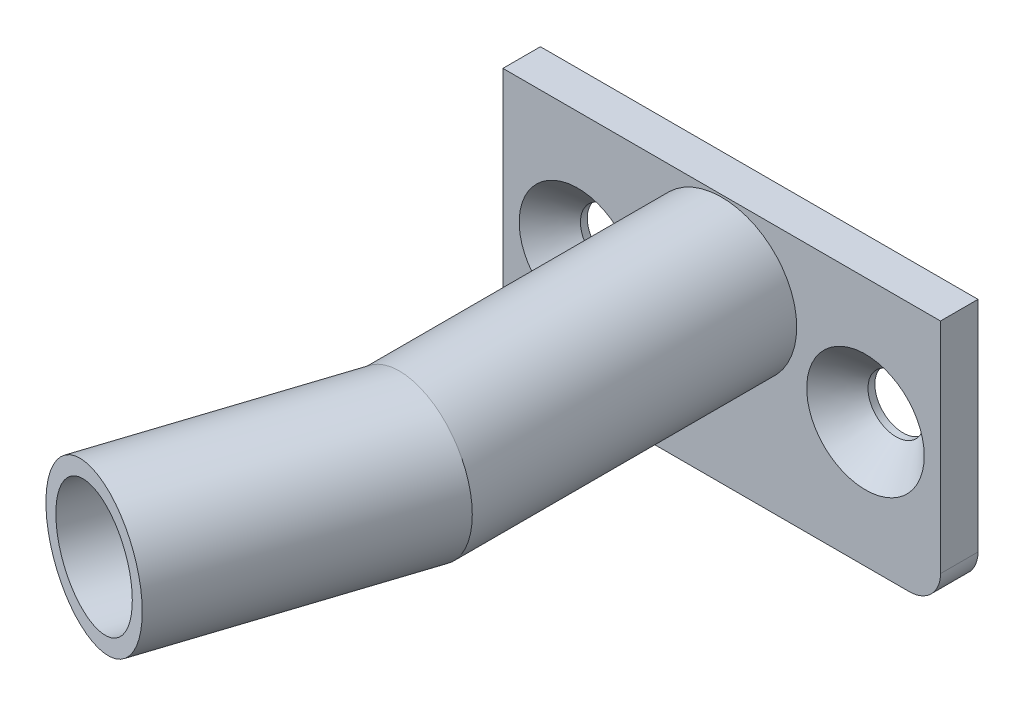
SolidWorks part; units mm, degrees
material "Ti-6Al-4VSolution treated and aged (SS)"
ref_plane "Top Plane" through (0, 0, 0) normal (0, 0, 1) x (1, 0, 0)
ref_plane "Front Plane" through (0, 0, 0) normal (0, 1, 0) x (1, 0, 0)
ref_plane "Right Plane" through (0, 0, 0) normal (1, 0, 0) x (0, 0, -1)
sketch "Sketch7" plane through (0, 0, 0) normal (0, 0, 1) x (1, 0, 0)
  line L1 (-17.5, -10) -> (17.5, -10)
  line L2 (-17.5, -10) -> (-17.5, 10)
  line L3 (-17.5, 10) -> (17.5, 10)
  line L4 (17.5, -10) -> (17.5, 10)
  line L5 (-17.5, -10) -> (17.5, 10) construction
  line L6 (-17.5, 10) -> (17.5, -10) construction
  point P0 (0, 0)
  dimension "D1" = 35
  dimension "D2" = 20
extrude "Boss-Extrude4" add sketch "Sketch7" along normal blind 3
fillet "Fillet1" radius 2.5 2 edges at (17.5, -10, 1.5) (-17.5, -10, 1.5)
sketch "Sketch8" plane through (0, 0, 3) normal (0, 0, 1) x (1, 0, 0)
  line L0 (-17.5, 1.25) -> (17.5, 1.25) construction
  line L1 (-17.5, 10) -> (-17.5, -7.5) construction
  line L2 (17.5, -7.5) -> (17.5, 10) construction
  line L3 (0, 10) -> (0, -10) construction
  line L4 (17.5, 10) -> (-17.5, 10) construction
  line L5 (-15, -10) -> (15, -10) construction
  circle A0 centre (0, 3.825) radius 6
  dimension "D1" = 12
  dimension "D2" = 6.175
extrude "Boss-Extrude5" add sketch "Sketch8" along normal blind 20
ref_axis "Axis1" through (0, 3.825, 23) along (0, 0, -1)
ref_plane "Plane1" through (0, 3.825, 0) normal (0, 1, 0) x (1, 0, 0)
sketch "Sketch9" plane through (0, 3.825, 0) normal (0, 1, 0) x (1, 0, 0)
  line L0 (0, -23) -> (0, -28)
  line L1 (-6, -23) -> (6, -23) construction
  line L2 (0, -23) -> (0, -3) construction
  line L3 (0, -28) -> (-1.5451, -32.7553)
  dimension "D1" = 5
  dimension "D2" = 162
  dimension "D3" = 5
sketch "Sketch10" plane through (0, 0, 23) normal (0, 0, 1) x (1, 0, 0)
  circle A1 centre (0, 3.825) radius 6
  circle A2 centre (0, 3.825) radius 6
  dimension "D1" = 0
sweep "Sweep3" add profiles "Sketch10" path "Sketch9"
sketch "Sketch11" plane through (-9.7741, 0, 30.0815) normal (-0.309, 0, 0.9511) x (0.9511, 0, 0.309)
  circle A0 centre (8.6525, 3.825) radius 4.7625
  circle A1 centre (8.6525, 3.825) radius 6
  circle A2 centre (8.6525, 3.825) radius 6
  dimension "D2" = 9.525
  dimension "D1" = 0
extrude "Boss-Extrude6" add sketch "Sketch11" along normal blind 15
hole_wizard "CSK for M4 Flat Head Machine Screw1" positions "Sketch12" profile "Sketch13" countersink size "M4" standard "ANSI Metric" end condition through all
sketch "Sketch12" plane through (0, 0, 3) normal (0, 0, 1) x (1, 0, 0)
  point P0 (-11.5, 0)
  point P2 (11.5, 0)
  dimension "D1" = 11.5
  dimension "D2" = 11.5
sketch "Sketch13" plane through (-11.5, 0, 3) normal (1, 0, 0) x (0, -1, 0)
  line L0 (0, 0) -> (0, 3)
  line L1 (0, 3) -> (2.25, 3)
  line L2 (2.25, 3) -> (2.25, 2.45)
  line L3 (2.25, 2.45) -> (4.7, 0)
  line L5 (4.7, 0) -> (0, 0)
  line L6 (-2.25, 2.45) -> (-4.7, 0) construction
  line L11 (0, -6.35) -> (0, 107.95) construction
  dimension "Thru Hole Dia." = 4.5
  dimension "Thru Hole Depth" = 3
  dimension "Near C'Sink Dia." = 9.4
  dimension "Near C'Sink Angle" = 90
